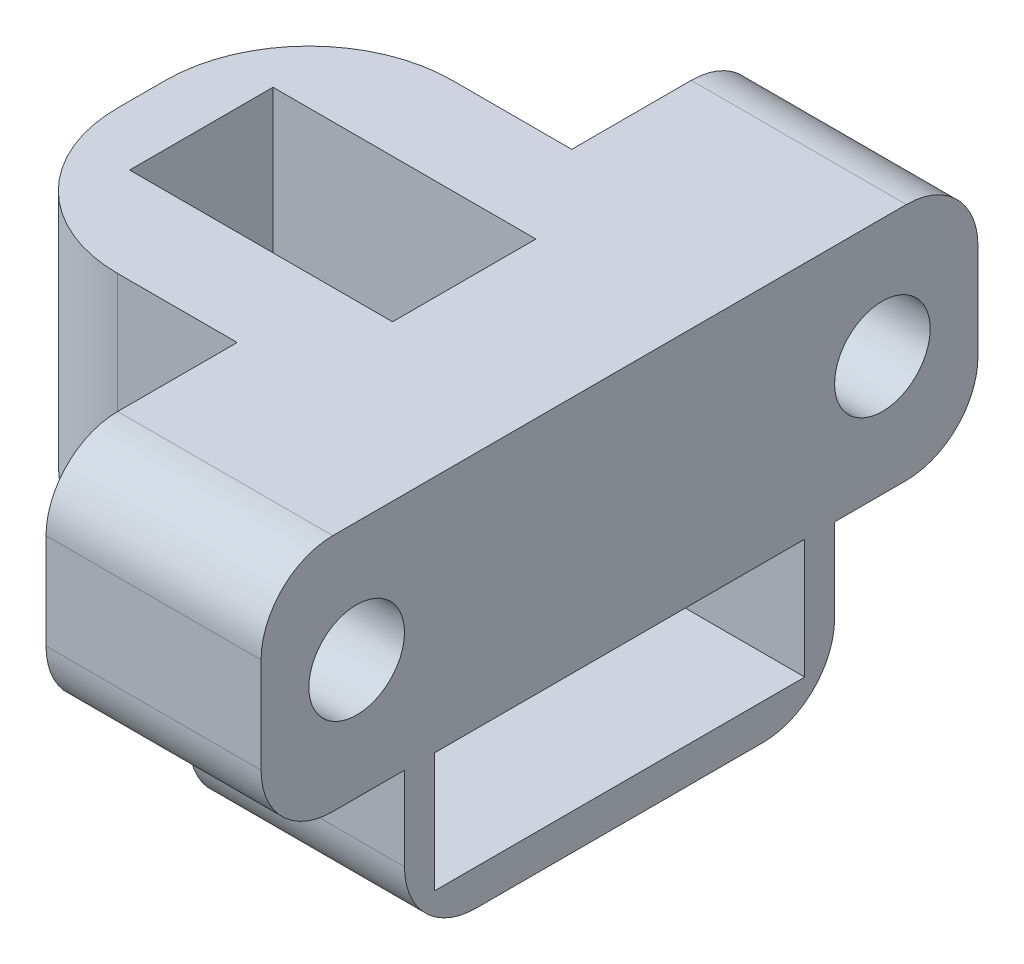
SolidWorks part; units mm, degrees
ref_plane "Plano frontal" through (0, 0, 0) normal (0, 0, 1) x (1, 0, 0)
ref_plane "Plano superior" through (0, 0, 0) normal (0, 1, 0) x (1, 0, 0)
ref_plane "Plano direito" through (0, 0, 0) normal (1, 0, 0) x (0, 0, -1)
sketch "Esboço1" plane through (0, 0, 0) normal (0, 1, 0) x (1, 0, 0)
  line L1 (-10, 15) -> (10, 15)
  line L2 (-10, 15) -> (-10, -15)
  line L3 (-10, -15) -> (10, -15)
  line L4 (10, 15) -> (10, -15)
  line L5 (-10, 15) -> (10, -15) construction
  line L6 (-10, -15) -> (10, 15) construction
  point P0 (0, 0)
  dimension "D1" = 30
  dimension "D2" = 20
extrude "Ressalto-extrusão1" add sketch "Esboço1" along normal blind 10
sketch "Esboço2" plane through (0, 10, 0) normal (0, 1, 0) x (1, 0, 0)
  line L1 (-10, 15) -> (1, 15)
  line L2 (-10, 15) -> (-10, 7)
  line L3 (-10, 7) -> (1, 7)
  line L4 (1, 15) -> (1, 7)
  line L5 (-10, -15) -> (1, -15)
  line L6 (-10, -15) -> (-10, -7)
  line L7 (-10, -7) -> (1, -7)
  line L8 (1, -15) -> (1, -7)
  dimension "D1" = 8
  dimension "D2" = 8
  dimension "D3" = 11
  dimension "D4" = 11
extrude "Corte-extrusão1" cut sketch "Esboço2" against normal blind 10
sketch "Esboço3" plane through (0, 10, 0) normal (0, 1, 0) x (1, 0, 0)
  line L0 (10, 0) -> (3.5, 0) construction
  line L1 (10, -15) -> (10, 15) construction
  line L2 (3.5, 0) -> (3.5, 3) construction
  line L4 (3.5, 3) -> (-7.5, 3)
  line L5 (3.5, 3) -> (3.5, -3)
  line L6 (3.5, -3) -> (-7.5, -3)
  line L7 (-7.5, 3) -> (-7.5, -3)
  dimension "D1" = 6.5
  dimension "D2" = 3
  dimension "D3" = 11
  dimension "D4" = 6
extrude "Corte-extrusão2" cut sketch "Esboço3" against normal blind 7
sketch "Esboço4" plane through (0, 0, 0) normal (0, -1, 0) x (1, 0, 0)
  line L0 (10, 0) -> (5.5, 0) construction
  line L1 (10, 15) -> (10, -15) construction
  line L3 (10, 9) -> (1, 9)
  line L4 (10, 9) -> (10, -9)
  line L5 (10, -9) -> (1, -9)
  line L6 (1, 9) -> (1, -9)
  line L7 (10, 9) -> (1, -9) construction
  line L8 (10, -9) -> (1, 9) construction
  dimension "D1" = 4.5
  dimension "D2" = 9
  dimension "D3" = 18
extrude "Ressalto-extrusão2" add sketch "Esboço4" along normal blind 6.5
sketch "Esboço5" plane through (10, 0, 0) normal (1, 0, 0) x (0, 0, -1)
  line L0 (9, 0) -> (-9, 0) construction
  line L1 (0, 0) -> (0, -2.5) construction
  line L3 (7.75, -5) -> (-7.75, -5)
  line L4 (7.75, -5) -> (7.75, 0)
  line L5 (7.75, 0) -> (-7.75, 0)
  line L6 (-7.75, -5) -> (-7.75, 0)
  line L7 (7.75, -5) -> (-7.75, 0) construction
  line L8 (7.75, 0) -> (-7.75, -5) construction
  dimension "D1" = 2.5
  dimension "D2" = 5
  dimension "D3" = 15.5
extrude "Corte-extrusão3" cut sketch "Esboço5" against normal blind 5.5
sketch "Esboço6" plane through (1, 0, 0) normal (-1, 0, 0) x (0, 0, 1)
  line L0 (-15, 5) -> (-7, 5) construction
  line L1 (-15, 0) -> (-15, 10) construction
  line L2 (-7, 0) -> (-7, 10) construction
  line L3 (15, 5) -> (7, 5) construction
  line L4 (15, 0) -> (15, 10) construction
  line L5 (7, 0) -> (7, 10) construction
  circle A0 centre (11, 5) radius 2
  circle A1 centre (-11, 5) radius 2
  dimension "D1" = 4
  dimension "D2" = 4
extrude "Corte-extrusão4" cut sketch "Esboço6" against normal through all
sketch "Esboço7" plane through (1, 0, 0) normal (-1, 0, 0) x (0, 0, 1)
  circle A0 centre (11, 5) radius 3.5
  circle A1 centre (-11, 5) radius 3.5
  dimension "D1" = 7
  dimension "D2" = 7
extrude "Corte-extrusão5" cut sketch "Esboço7" against normal blind 2
fillet "Filete1" radius 6 2 edges at (-10, 5, -7) (-10, 5, 7)
fillet "Filete2" radius 3 6 edges at (5.5, 10, 15) (5.5, 10, -15) (5.5, 0, -15) (5.5, 0, 15) (5.5, -6.5, 9) (5.5, -6.5, -9)
